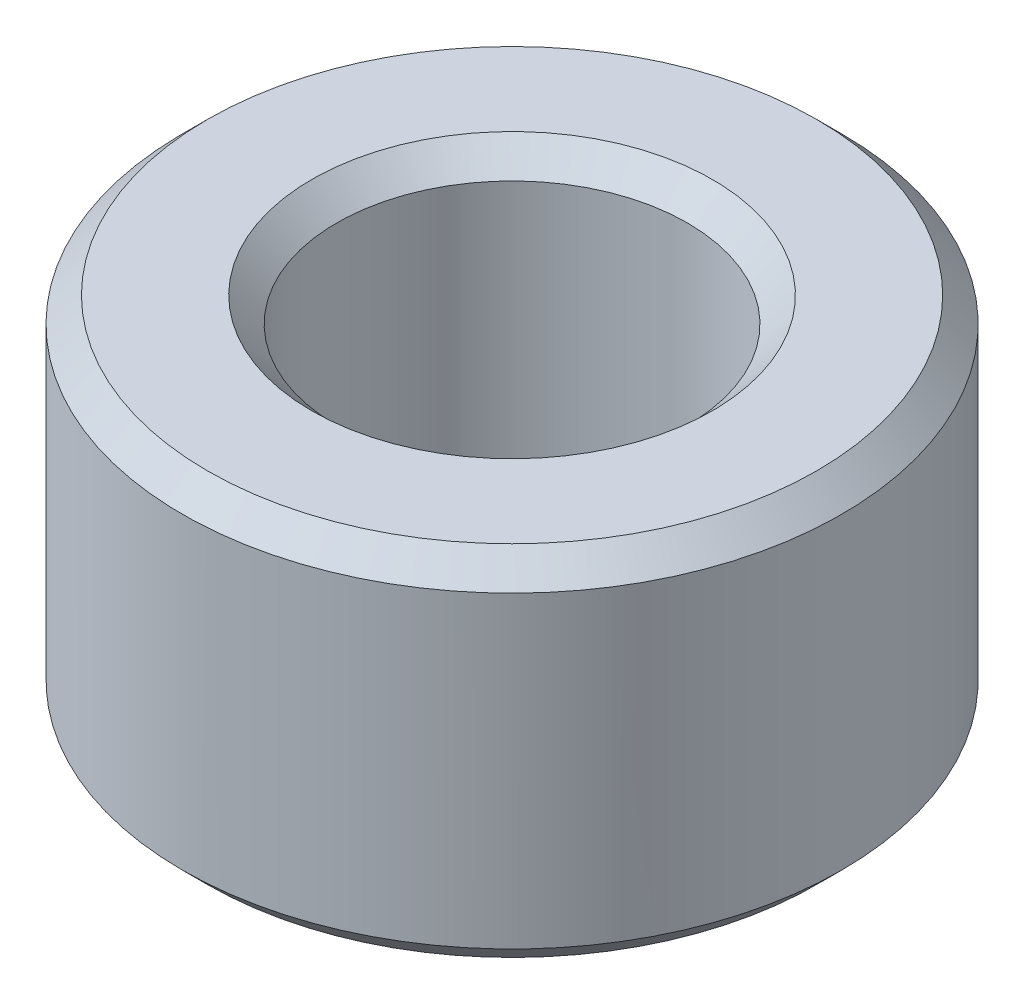
SolidWorks part; units mm, degrees
ref_plane "Front Plane" through (0, 0, 0) normal (0, 0, 1) x (1, 0, 0)
ref_plane "Top Plane" through (0, 0, 0) normal (0, 1, 0) x (1, 0, 0)
ref_plane "Right Plane" through (0, 0, 0) normal (1, 0, 0) x (0, 0, -1)
sketch "Sketch1" plane through (0, 0, 0) normal (0, 1, 0) x (1, 0, 0)
  circle A0 centre (0, 0) radius 40
  dimension "SLEEVE_OD" = 80
extrude "Boss-Extrude1" add sketch "Sketch1" along normal blind 43.4859
sketch "Sketch2" plane through (0, 0, 0) normal (0, 1, 0) x (1, 0, 0)
  circle A0 centre (0, 0) radius 21.2775
  dimension "BORE_D" = 42.5549
extrude "Cut-Extrude1" cut sketch "Sketch2" along normal through all
chamfer "Chamfer1" distance 3.0422 angle 45 4 edges at (0, 43.4859, 21.2775) (0, 0, 21.2775) (0, 0, 40) (0, 43.4859, 40)
